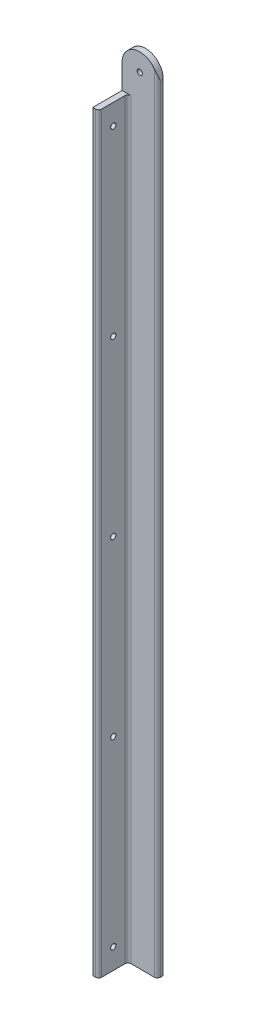
SolidWorks part; units mm, degrees
material "6061 Alloy"
ref_plane "Front Plane" through (0, 0, 0) normal (0, 0, 1) x (1, 0, 0)
ref_plane "Top Plane" through (0, 0, 0) normal (0, 1, 0) x (1, 0, 0)
ref_plane "Right Plane" through (0, 0, 0) normal (1, 0, 0) x (0, 0, -1)
sketch "Sketch2" plane through (0, 0, 0) normal (0, 1, 0) x (1, 0, 0)
  line L0 (0, 0) -> (19.05, 0)
  line L1 (0, 0) -> (0, 19.05)
  line L2 (4.7625, 3.175) -> (17.4625, 3.175)
  line L3 (3.175, 4.7625) -> (3.175, 17.4625)
  line L4 (0, 19.05) -> (1.5875, 19.05)
  line L5 (19.05, 1.5875) -> (19.05, 0)
  line L6 (3.175, 3.175) -> (3.175, 19.05) construction
  line L7 (3.175, 3.175) -> (19.05, 3.175) construction
  arc A0 (3.175, 17.4625) -> (1.5875, 19.05) centre (1.5875, 17.4625) ccw
  arc A1 (3.175, 4.7625) -> (4.7625, 3.175) centre (4.7625, 4.7625) ccw
  arc A2 (17.4625, 3.175) -> (19.05, 1.5875) centre (17.4625, 1.5875) cw
  dimension "D2" = 1.5875
  dimension "D1" = 3.175
extrude "Boss-Extrude1" add sketch "Sketch2" along normal blind 431.8
sketch "Sketch4" plane through (3.175, 0, 0) normal (1, 0, 0) x (0, 0, -1)
  line L0 (19.05, 431.8) -> (19.05, 406.4)
  line L1 (19.05, 431.8) -> (19.05, 0) construction
  line L2 (19.05, 406.4) -> (3.175, 406.4)
  line L3 (3.175, 431.8) -> (3.175, 0) construction
  line L4 (3.175, 406.4) -> (3.175, 431.8)
  line L5 (3.175, 431.8) -> (19.05, 431.8)
extrude "Cut-Extrude1" cut sketch "Sketch4" against normal blind 6.35
sketch "Sketch5" plane through (3.175, 0, 0) normal (-1, 0, 0) x (0, 0, 1)
  line L8 (-4.7625, 406.4) -> (-3.175, 406.4)
  line L9 (-3.175, 406.4) -> (-3.175, 431.8)
  line L10 (-3.175, 431.8) -> (-4.7625, 431.8)
  line L11 (-4.7625, 431.8) -> (-4.7625, 406.4)
  line L12 (-4.7625, 406.4) -> (-3.175, 406.4)
  line L13 (-3.175, 406.4) -> (-3.175, 431.8)
  line L14 (-3.175, 431.8) -> (-4.7625, 431.8)
  line L15 (-4.7625, 431.8) -> (-4.7625, 406.4)
  dimension "D1" = 0
extrude "Cut-Extrude2" cut sketch "Sketch5" against normal blind 6.35
sketch "Sketch6" plane through (3.175, 0, 0) normal (1, 0, 0) x (0, 0, -1)
  line L0 (19.05, 0) -> (3.175, 0) construction
  line L1 (11.1125, 0) -> (11.1125, 15.875) construction
  line L2 (19.05, 406.4) -> (3.175, 406.4) construction
  line L3 (11.1125, 406.4) -> (11.1125, 390.525) construction
  line L4 (11.1125, 15.875) -> (11.1125, 203.2) construction
  line L5 (11.1125, 203.2) -> (11.1125, 390.525) construction
  circle A1 centre (11.1125, 109.5375) radius 1.4224
  circle A2 centre (11.1125, 203.2) radius 1.4224
  circle A3 centre (11.1125, 296.8625) radius 1.4224
  circle A5 centre (11.1125, 11.1125) radius 1.4224
  circle A6 centre (11.1125, 395.2875) radius 1.4224
  point P12 (11.1125, 203.2)
  point P13 (11.1125, 296.8625)
  point P15 (11.1125, 109.5375)
  dimension "D2" = 2.8448
  dimension "D3" = 2.8448
  dimension "D4" = 2.8448
  dimension "D6" = 2.8448
  dimension "D7" = 2.8448
extrude "Cut-Extrude3" cut sketch "Sketch6" against normal blind 5.08
sketch "Sketch7" plane through (0, 431.8, 0) normal (0, 1, 0) x (1, 0, 0)
  line L8 (17.4625, 3.175) -> (0, 3.175)
  line L9 (0, 3.175) -> (0, 0)
  line L10 (0, 0) -> (19.05, 0)
  line L11 (19.05, 0) -> (19.05, 1.5875)
  line L12 (17.4625, 3.175) -> (0, 3.175)
  line L13 (0, 3.175) -> (0, 0)
  line L14 (0, 0) -> (19.05, 0)
  line L15 (19.05, 0) -> (19.05, 1.5875)
  arc A2 (19.05, 1.5875) -> (17.4625, 3.175) centre (17.4625, 1.5875) ccw
  arc A3 (19.05, 1.5875) -> (17.4625, 3.175) centre (17.4625, 1.5875) ccw
  dimension "D1" = 0
extrude "Cut-Extrude4" cut sketch "Sketch7" against normal blind 2.54
sketch "Sketch8" plane through (0, 0, -3.175) normal (0, 0, -1) x (-1, 0, 0)
  line L0 (0, 429.26) -> (0, 419.735) construction
  line L1 (0, 429.26) -> (0, 406.4) construction
  line L2 (0, 419.735) -> (-9.525, 419.735) construction
  circle A0 centre (-9.525, 419.735) radius 1.4224
  dimension "D1" = 2.8448
extrude "Cut-Extrude5" cut sketch "Sketch8" against normal blind 5.08
ref_plane "Plane1" through (0, 0, 2.54) normal (0, 0, 1) x (1, 0, 0)
mirror "Mirror3" about plane through (0, 0, 2.54) normal (0, 0, 1) of bodies 106
sketch "Sketch9" plane through (0, 0, 2.54) normal (0, 0, 1) x (1, 0, 0)
  line L1 (-6.6248, 469.5409) -> (22.2362, 469.5409)
  line L2 (-6.6248, 469.5409) -> (-6.6248, -77.9837)
  line L3 (-6.6248, -77.9837) -> (22.2362, -77.9837)
  line L4 (22.2362, 469.5409) -> (22.2362, -77.9837)
extrude "Cut-Extrude6" cut sketch "Sketch9" against normal blind 30.48
sketch "Sketch10" plane through (0, 0, 8.255) normal (0, 0, 1) x (1, 0, 0)
  line L0 (9.525, 419.735) -> (9.525, 415.925) construction
  line L6 (9.525, 419.735) -> (0, 429.26) construction
  line L9 (19.05, 419.735) -> (19.05, 429.26)
  line L10 (19.05, 429.26) -> (0, 429.26)
  line L11 (0, 419.735) -> (0, 429.26)
  line L13 (19.05, 429.26) -> (9.525, 419.735) construction
  arc A3 (19.05, 419.735) -> (0, 419.735) centre (9.525, 419.735) ccw
  line M4 (17.4625, 429.26) -> (0, 429.26)
  line M5 (0, 429.26) -> (0, 406.4)
  line M9 (17.4625, 0) -> (17.4625, 429.26)
extrude "Cut-Extrude7" cut sketch "Sketch10" against normal blind 5.08 contours M9 | M9 M4 | M5 region at (18.3487, 426.1569, 8.255) region at (2.1276, 427.1324, 8.255) region at (15.5776, 428.0522, 8.255)
